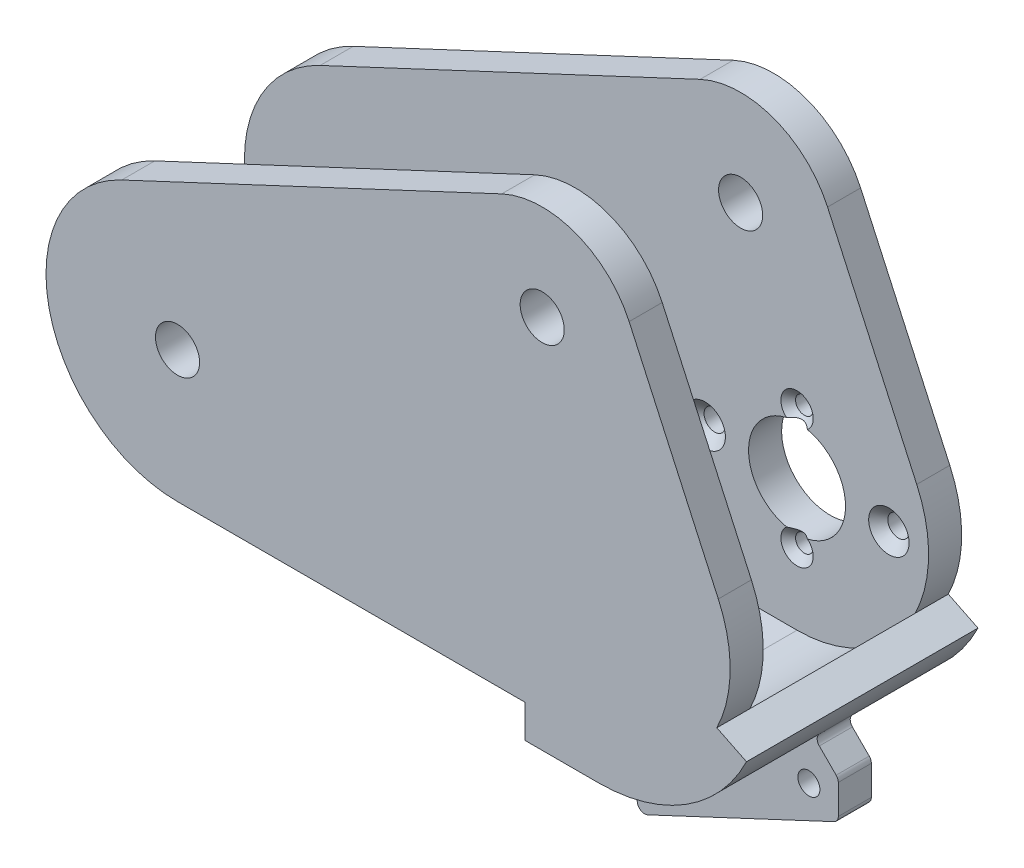
SolidWorks part; units mm, degrees
ref_plane "Front Plane" through (0, 0, 0) normal (0, 0, 1) x (1, 0, 0)
ref_plane "Top Plane" through (0, 0, 0) normal (0, 1, 0) x (1, 0, 0)
ref_plane "Right Plane" through (0, 0, 0) normal (1, 0, 0) x (0, 0, -1)
sketch "Sketch1" plane through (0, 0, 0) normal (0, 0, 1) x (1, 0, 0)
  circle A0 centre (0, 0) radius 6.6
  circle A1 centre (0, 0) radius 17.9
  dimension "D1" = 13.2
  dimension "D2" = 35.8
extrude "Boss-Extrude1" add sketch "Sketch1" along normal blind 4.5
sketch "Sketch2" plane through (0, 0, 4.5) normal (0, 0, 1) x (1, 0, 0)
  line L0 (12.5, 0) -> (-12.5, 0) construction
  point P0 (-12.5, 0)
  point P6 (0, 0)
  point P8 (12.5, 0)
  dimension "D1" = 25
hole_wizard "CSK for M2.5 Flat Head Machine Screw2" positions "Sketch5" profile "Sketch6" countersink size "M2.5" standard "ANSI Metric"
sketch "Sketch5" plane through (0, 0, 4.5) normal (0, 0, 1) x (1, 0, 0)
  point P0 (-12.5, 0)
  point P3 (12.5, 0)
sketch "Sketch6" plane through (-12.5, 0, 4.5) normal (1, 0, 0) x (0, -1, 0)
  line L0 (0, 0) -> (0, 5.3712)
  line L1 (0, 5.3712) -> (1.45, 4.5)
  line L2 (1.45, 4.5) -> (1.45, 1.3)
  line L3 (1.45, 1.3) -> (2.75, 0)
  line L5 (2.75, 0) -> (0, 0)
  line L6 (-1.45, 1.3) -> (-2.75, 0) construction
  line L10 (0, 5.3712) -> (-1.45, 4.5) construction
  line L11 (0, -6.35) -> (0, 107.95) construction
  dimension "Hole Dia." = 2.9
  dimension "Hole Depth" = 4.5
  dimension "Near C'Sink Dia." = 5.5
  dimension "Near C'Sink Angle" = 90
  dimension "Drill Angle" = 118
hole_wizard "CSK for M2 Flat Head Machine Screw1" positions "Sketch12" profile "Sketch13" countersink size "M2" standard "ANSI Metric"
sketch "Sketch12" plane through (0, 0, 4.5) normal (0, 0, 1) x (1, 0, 0)
  line L0 (0, 0) -> (0, 8.125) construction
  line L3 (0, 0) -> (0, -8.125) construction
  point P2 (0, 8.125)
  point P9 (0, -8.125)
  dimension "D1" = 16.25
sketch "Sketch13" plane through (0, -8.125, 4.5) normal (1, 0, 0) x (0, -1, 0)
  line L0 (0, 0) -> (0, 7.071)
  line L1 (0, 7.071) -> (1.2, 6.35)
  line L2 (1.2, 6.35) -> (1.2, 1)
  line L3 (1.2, 1) -> (2.2, 0)
  line L5 (2.2, 0) -> (0, 0)
  line L6 (-1.2, 1) -> (-2.2, 0) construction
  line L10 (0, 7.071) -> (-1.2, 6.35) construction
  line L11 (0, -6.35) -> (0, 107.95) construction
  dimension "Hole Dia." = 2.4
  dimension "Hole Depth" = 6.35
  dimension "Near C'Sink Dia." = 4.4
  dimension "Near C'Sink Angle" = 90
  dimension "Drill Angle" = 118
sketch "Sketch7" plane through (0, 0, 4.5) normal (0, 0, 1) x (1, 0, 0)
  line L0 (0, -17.9) -> (-57.2987, -17.9)
  line L1 (-57.2987, 17.9) -> (0, 17.9)
  line L2 (-57.2987, 0) -> (0, 0) construction
  circle A0 centre (0, 0) radius 17.9 construction
  arc A1 (-57.2987, -17.9) -> (-57.2987, 17.9) centre (-57.2987, 0) cw
  arc A2 (0, 17.9) -> (0, -17.9) centre (0, 0) ccw
  point P6 (-57.2987, 0)
extrude "Boss-Extrude3" add sketch "Sketch7" against normal up to surface (4.5 mm away) up to face at (1.2, 8.125, 0)
sketch "Sketch8" plane through (0, 0, 4.5) normal (0, 0, 1) x (1, 0, 0)
  circle A0 centre (-57.2987, 0) radius 3
  dimension "D1" = 6
extrude "Cut-Extrude1" cut sketch "Sketch8" against normal up to surface (4.5 mm away) contours A0 up to face at (1.2, 8.125, 0)
sketch "Sketch10" plane through (0, 0, 0) normal (0, 0, -1) x (-1, 0, 0)
  line L0 (13.19, 40.4223) -> (64.8902, 16.2104)
  line L1 (-4.1521, 34.0422) -> (-16.2871, 7.4256)
  line L2 (57.2987, 17.9) -> (0, 17.9) construction
  line L3 (57.2987, 17.9) -> (0, 17.9)
  arc A0 (13.19, 40.4223) -> (-4.1521, 34.0422) centre (7.6766, 28.6493) ccw
  arc A1 (0, 17.9) -> (0, -17.9) centre (0, 0) ccw construction
  arc A2 (57.2987, -17.9) -> (57.2987, 17.9) centre (57.2987, 0) ccw construction
  circle A3 centre (7.6766, 28.6493) radius 3 construction
  arc A4 (0, 17.9) -> (-16.2871, 7.4256) centre (0, 0) ccw
  arc A5 (64.8902, 16.2104) -> (57.2987, 17.9) centre (57.2987, 0) ccw
  circle A7 centre (7.6766, 28.6493) radius 3
  dimension "D1" = 10
extrude "Boss-Extrude4" add sketch "Sketch10" against normal up to surface (4.5 mm away) up to face at (-54.2987, 0, 4.5)
sketch "Sketch15" plane through (0, 0, 0) normal (0, 0, -1) x (-1, 0, 0)
  line L0 (57.2987, -17.9) -> (0, -17.9) construction
  line L1 (10, -17.9) -> (0, -17.9)
  line L2 (10, -22.4) -> (0, -22.4)
  line L3 (10, -17.9) -> (10, -22.4)
  line L4 (-16.081, -7.862) -> (-20.1238, -9.8384)
  line L5 (57.2987, -22.4) -> (0, -22.4) construction
  line L6 (57.2987, -17.9) -> (0, -17.9) construction
  arc A0 (-16.2871, 7.4256) -> (0, -17.9) centre (0, 0) ccw construction
  arc A1 (-16.081, -7.862) -> (0, -17.9) centre (0, 0) ccw
  arc A2 (-20.1238, -9.8384) -> (0, -22.4) centre (0, 0) ccw
  arc A3 (-20.3816, 9.2924) -> (0, -22.4) centre (0, 0) ccw construction
  arc A4 (-16.2871, 7.4256) -> (0, -17.9) centre (0, 0) ccw construction
  dimension "D2" = 10
  dimension "D3" = 25
  dimension "D1" = 4.5
extrude "Boss-Extrude5" add sketch "Sketch15" against normal up to surface (27 mm away)
sketch "Sketch16" plane through (0, 0, 27) normal (0, 0, 1) x (1, 0, 0)
  line L0 (4.1521, 34.0422) -> (16.2871, 7.4256) construction
  line L1 (-64.8902, 16.2104) -> (-13.19, 40.4223) construction
  line L2 (16.081, -7.862) -> (20.1238, -9.8384) construction
  line L3 (0, -22.4) -> (-10, -22.4) construction
  line L4 (-10, -22.4) -> (-10, -17.9) construction
  line L5 (-57.2987, -17.9) -> (-10, -17.9) construction
  line L6 (4.1521, 34.0422) -> (16.2871, 7.4256)
  line L7 (-64.8902, 16.2104) -> (-13.19, 40.4223)
  line L8 (16.081, -7.862) -> (20.1238, -9.8384)
  line L9 (0, -22.4) -> (-10, -22.4)
  line L10 (-10, -22.4) -> (-10, -17.9)
  line L11 (-57.2987, -17.9) -> (-10, -17.9)
  arc A0 (4.1521, 34.0422) -> (-13.19, 40.4223) centre (-7.6766, 28.6493) ccw construction
  arc A1 (16.081, -7.862) -> (16.2871, 7.4256) centre (0, 0) ccw construction
  arc A2 (0, -22.4) -> (20.1238, -9.8384) centre (0, 0) ccw construction
  circle A3 centre (-57.2987, 0) radius 3 construction
  arc A4 (-64.8902, 16.2104) -> (-57.2987, -17.9) centre (-57.2987, 0) ccw construction
  arc A5 (4.1521, 34.0422) -> (-13.19, 40.4223) centre (-7.6766, 28.6493) ccw
  arc A6 (16.081, -7.862) -> (16.2871, 7.4256) centre (0, 0) ccw
  arc A7 (0, -22.4) -> (20.1238, -9.8384) centre (0, 0) ccw
  circle A8 centre (-57.2987, 0) radius 3
  arc A9 (-64.8902, 16.2104) -> (-57.2987, -17.9) centre (-57.2987, 0) ccw
  circle A10 centre (-7.6766, 28.6493) radius 3 construction
  circle A11 centre (-7.6766, 28.6493) radius 3
extrude "Boss-Extrude6" add sketch "Sketch16" along normal blind 4.5
ref_plane "Plane1" through (0, 0, 15.75) normal (0, 0, 1) x (1, 0, 0)
sketch "Sketch17" plane through (0, 0, 15.75) normal (0, 0, 1) x (1, 0, 0)
  line L0 (-10, -22.4) -> (0, -22.4) construction
  line L1 (-10, -22.4) -> (0, -22.4)
  line L2 (-10, -22.4) -> (-8.054, -36.8986)
  line L3 (-8.054, -36.8986) -> (19.1143, -24.1753)
  line L5 (19.1143, -24.1753) -> (19.1143, -19.1143)
  line L6 (19.1143, -19.1143) -> (15.8392, -15.8392)
  line L7 (-4.8146, -30.9646) -> (15.1143, -21.6317) construction
  line L8 (-13.19, 40.4223) -> (-64.8902, 16.2104) construction
  arc A0 (0, -22.4) -> (20.1238, -9.8384) centre (0, 0) ccw construction
  arc A1 (0, -22.4) -> (15.8392, -15.8392) centre (0, 0) ccw
  circle A2 centre (-4.8146, -30.9646) radius 1.5
  circle A3 centre (15.1143, -21.6317) radius 1.5
  point P12 (-10, -30.4)
  point P13 (-10, -30.4)
  point P14 (-10, -32.5883)
  point P17 (19.1143, -23.7878)
  dimension "D5" = 4
  dimension "D6" = 4
  dimension "D7" = 3
  dimension "D1" = 30
  dimension "D2" = 30
  dimension "D3" = 135
  dimension "D4" = 4
extrude "Boss-Extrude7" add sketch "Sketch17" along normal mid plane 4.5
fillet "Fillet1" radius 1 4 edges at (15.8392, -15.8392, 15.75) (19.1143, -19.1143, 15.75) (19.1143, -24.1753, 15.75) (-8.054, -36.8986, 15.75)
